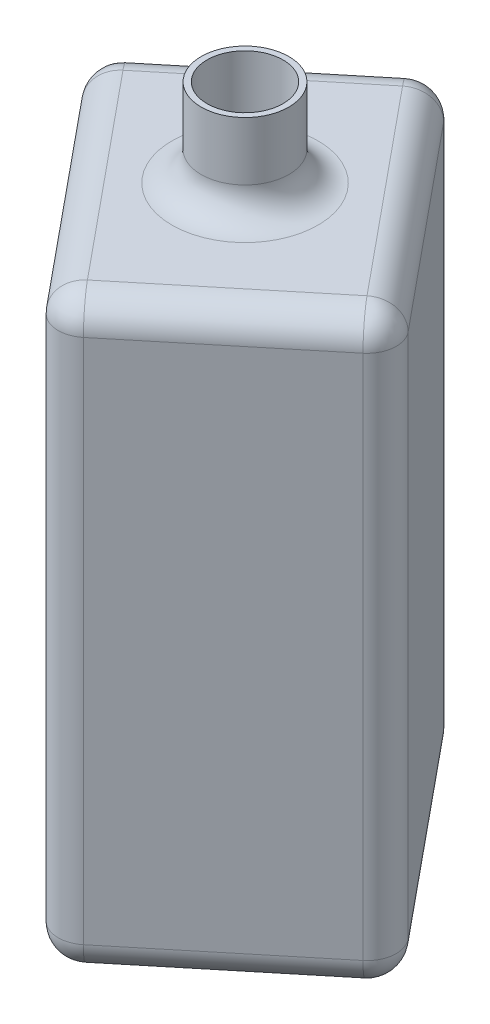
SolidWorks part; units mm, degrees
ref_plane "Front Plane" through (0, 0, 0) normal (0, 0, 1) x (1, 0, 0)
ref_plane "Top Plane" through (0, 0, 0) normal (0, 1, 0) x (1, 0, 0)
ref_plane "Right Plane" through (0, 0, 0) normal (1, 0, 0) x (0, 0, -1)
sketch "Sketch1" plane through (0, 0, 0) normal (0, 1, 0) x (1, 0, 0)
  line L0 (54.3114, -12.5438) -> (-1.7829, 55.7126)
  line L1 (54.3114, -12.5438) -> (1.7829, -55.7126)
  line L2 (-1.7829, 55.7126) -> (-54.3114, 12.5438)
  line L3 (1.7829, -55.7126) -> (-54.3114, 12.5438)
  line L4 (54.3114, -12.5438) -> (-54.3114, 12.5438) construction
  line L5 (-1.7829, 55.7126) -> (1.7829, -55.7126) construction
  line L6 (-0.4064, 69.7876) -> (-68.3864, 13.9204)
  line L7 (0.4064, -69.7876) -> (-68.3864, 13.9204)
  line L8 (68.3864, -13.9204) -> (0.4064, -69.7876)
  line L9 (68.3864, -13.9204) -> (-0.4064, 69.7876)
  point P1 (0, 0)
  dimension "D1" = 10
extrude "Boss-Extrude2" add sketch "Sketch1" along normal blind 200
extrude "Boss-Extrude3" add sketch "Sketch1<2>" along normal blind 200
sketch "Sketch1<2>" plane through (0, 0, 0) normal (0, 1, 0) x (1, 0, 0) same geometry as "Sketch1"
extrude "Boss-Extrude4" add sketch "Sketch1<4>" along normal blind 200
sketch "Sketch1<4>" plane through (0, 0, 0) normal (0, 1, 0) x (1, 0, 0) same geometry as "Sketch1"
sketch "Sketch2" plane through (33.99, 0, -27.9336) normal (0.7726, 0, -0.6349) x (-0.6349, 0, -0.7726)
  line L0 (54.1744, 200) -> (54.1744, 0) construction
  line L1 (-54.1744, 0) -> (54.1744, 0)
  line L2 (-54.1744, 0) -> (-54.1744, 6.4245)
  line L3 (-54.1744, 6.4245) -> (54.1744, 6.4245)
  line L4 (54.1744, 0) -> (54.1744, 6.4245)
  line L6 (54.1744, 194.5987) -> (-54.1744, 194.5987)
  line L7 (54.1744, 194.5987) -> (54.1744, 200)
  line L8 (54.1744, 200) -> (-54.1744, 200)
  line L9 (-54.1744, 194.5987) -> (-54.1744, 200)
extrude "Boss-Extrude5" add sketch "Sketch2" against normal up to next
sketch "Sketch3" plane through (0, 200, 0) normal (0, 1, 0) x (1, 0, 0)
  circle A0 centre (0, 0) radius 15
  circle A1 centre (0, 0) radius 13
  dimension "D1" = 2
extrude "Boss-Extrude6" add sketch "Sketch3" along normal blind 30
fillet "Fillet4" radius 10 1 edges at (0, 200, 15) type face fillet first side face at (0, 230, 15) second side face at (0, 200, 15)
fillet "Fillet5" radius 10 12 edges at (-33.99, 0, 27.9336) (-68.3864, 100, -13.9204) (-34.3964, 0, -41.854) (0.4064, 100, 69.7876) (34.3964, 0, 41.854) (68.3864, 100, 13.9204) (-0.4064, 100, -69.7876) (33.99, 0, -27.9336) (34.3964, 200, 41.854) (-33.99, 200, 27.9336) (-34.3964, 200, -41.854) (33.99, 200, -27.9336)
